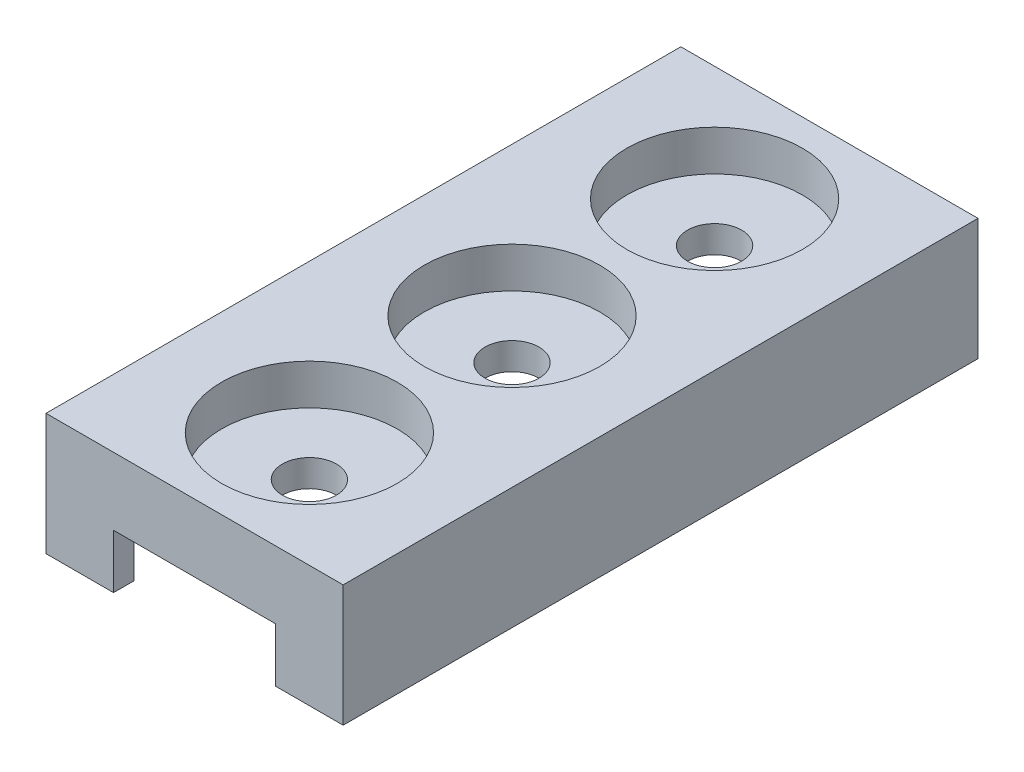
SolidWorks part; units mm, degrees
ref_plane "Front Plane" through (0, 0, 0) normal (0, 0, 1) x (1, 0, 0)
ref_plane "Top Plane" through (0, 0, 0) normal (0, 1, 0) x (1, 0, 0)
ref_plane "Right Plane" through (0, 0, 0) normal (1, 0, 0) x (0, 0, -1)
sketch "Sketch2" plane through (0, 0, 0) normal (0, 1, 0) x (1, 0, 0)
  line L0 (0, 23.5) -> (0, 21.5) construction
  line L1 (-11, -23.5) -> (11, -23.5)
  line L2 (-11, -23.5) -> (-11, 23.5)
  line L3 (-11, 23.5) -> (11, 23.5)
  line L4 (11, -23.5) -> (11, 23.5)
  line L5 (0, 8.5) -> (0, 6.5) construction
  line L6 (-11, 0) -> (11, 0) construction
  line L7 (0, -21.5) -> (0, -23.5) construction
  line L8 (0, -6.5) -> (0, -8.5) construction
  circle A0 centre (0, 0) radius 6.5
  circle A1 centre (0, 15) radius 6.5
  circle A2 centre (0, -15) radius 6.5
  dimension "D3" = 13
  dimension "D1" = 47
  dimension "D2" = 22
extrude "Boss-Extrude1" add sketch "Sketch2" along normal blind 3 contours A2 L2 L1 L4 L3 A1 A0 region at (-10.4811, 0, 0)
sketch "Sketch3" plane through (0, 0, 0) normal (0, -1, 0) x (1, 0, 0)
  line L1 (-11, 23.5) -> (11, 23.5)
  line L2 (-11, 23.5) -> (-11, -23.5)
  line L3 (-11, -23.5) -> (11, -23.5)
  line L4 (11, 23.5) -> (11, -23.5)
extrude "Boss-Extrude2" add sketch "Sketch3" along normal blind 2
sketch "Sketch5" plane through (0, -2, 0) normal (0, -1, 0) x (-1, 0, 0)
  line L0 (11, 0) -> (9, 0) construction
  line L1 (9, -22) -> (-9, -22)
  line L2 (9, -22) -> (9, 22)
  line L3 (9, 22) -> (-9, 22)
  line L4 (-9, -22) -> (-9, 22)
  line L5 (11, -23.5) -> (-11, -23.5)
  line L6 (11, -23.5) -> (11, 23.5)
  line L7 (11, 23.5) -> (-11, 23.5)
  line L8 (-11, -23.5) -> (-11, 23.5)
  line L9 (0, 23.5) -> (0, 22) construction
  line L10 (0, -23.5) -> (0, -22) construction
  line L11 (11, 23.5) -> (-11, 23.5) construction
  line L12 (-9, 0) -> (-11, 0) construction
  line L13 (-9, -22) -> (-9, -23.5)
  line L14 (0, -31.1477) -> (0, 7.1093) construction
  line L15 (9, -22) -> (9, -23.5)
  line L16 (-9, -22) -> (-6, -22)
  line L17 (9, -23.5) -> (6, -23.5)
  line L18 (9, -23.5) -> (9, -22)
  line L19 (9, -22) -> (6, -22)
  line L20 (6, -23.5) -> (6, -22)
  line L21 (-6, -23.5) -> (-6, -22)
  line L22 (-9, -23.5) -> (-6, -23.5)
  line L23 (-9, -23.5) -> (-9, -22)
  line L25 (-6, -22) -> (6, -22)
  line L26 (-6, -22) -> (-6, -23.5)
  line L27 (-6, -23.5) -> (6, -23.5)
  line L28 (6, -22) -> (6, -23.5)
  line L29 (-6, -22) -> (6, -22)
  line L30 (-6, -22) -> (-6, -23.5)
  line L31 (-6, -23.5) -> (6, -23.5)
  line L32 (6, -22) -> (6, -23.5)
  circle A0 centre (0, -15) radius 2
  circle A1 centre (0, 15) radius 2
  circle A2 centre (0, 0) radius 2
  line M10 (11, -23.5) -> (11, 23.5)
  line M11 (11, 23.5) -> (-11, 23.5)
  line M12 (-11, 23.5) -> (-11, -23.5)
  line M13 (-11, -23.5) -> (11, -23.5)
  dimension "D1" = 12
  dimension "D2" = 18
  dimension "D3" = 44
extrude "Boss-Extrude3" add sketch "Sketch5" along normal blind 4 contours L2 L15 L13 L4 L3 M13 M10 M11 M12 region at (-9.5189, -2, 0)
extrude "Boss-Extrude6" add sketch "Sketch5<5>" against normal blind 1 contours A2 region at (0, -2, 0)
sketch "Sketch5<5>" plane through (0, -2, 0) normal (0, -1, 0) x (-1, 0, 0) same geometry as "Sketch5"
extrude "Cut-Extrude1" cut sketch "Sketch5<6>" against normal blind 2 contours A2 | A0 | A1 region at (0, -2, 15) region at (0, -2, -15) region at (0, -2, 0)
sketch "Sketch5<6>" plane through (0, -2, 0) normal (0, -1, 0) x (-1, 0, 0) same geometry as "Sketch5"
extrude "Boss-Extrude7" add sketch "Sketch5<7>" along normal blind 4 contours L20 L15 L1 M13 | L5 L21 L1 L13 region at (-7.5, -2, 22.75) region at (7.5, -2, 22.75)
sketch "Sketch5<7>" plane through (0, -2, 0) normal (0, -1, 0) x (-1, 0, 0) same geometry as "Sketch5"
